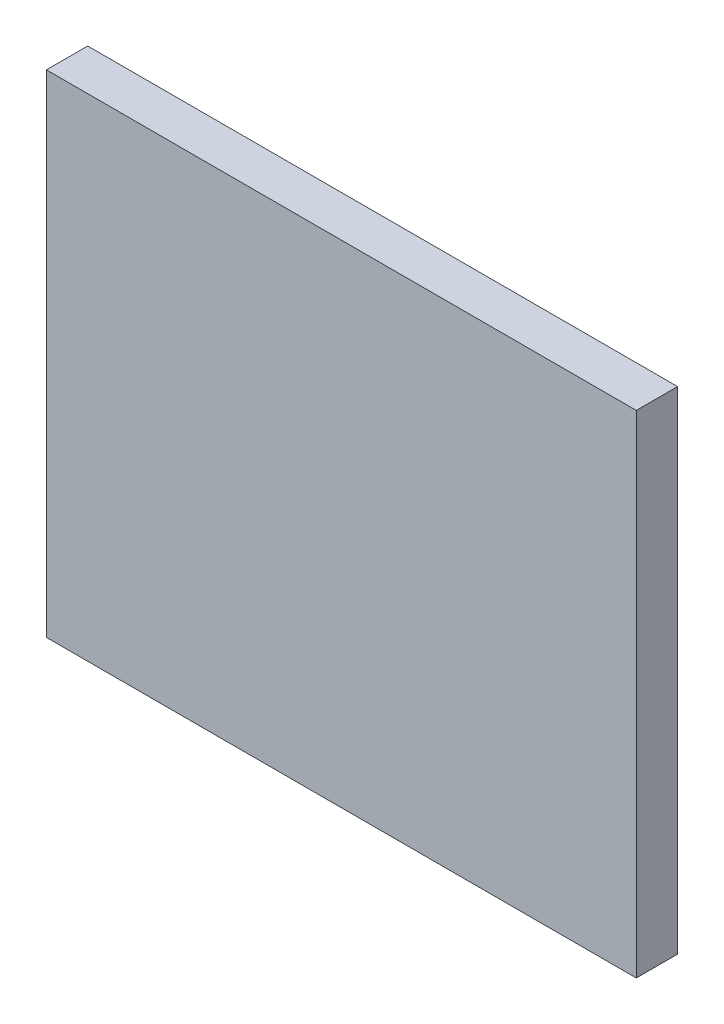
SolidWorks part; units mm, degrees
material "Buche"
ref_plane "Ebene vorne" through (0, 0, 0) normal (0, 0, 1) x (1, 0, 0)
ref_plane "Ebene oben" through (0, 0, 0) normal (0, 1, 0) x (1, 0, 0)
ref_plane "Ebene rechts" through (0, 0, 0) normal (1, 0, 0) x (0, 0, -1)
sketch "Skizze1" plane through (0, 0, 0) normal (0, 0, 1) x (1, 0, 0)
  line L1 (0, 0) -> (300, 0)
  line L2 (0, 0) -> (0, 250)
  line L3 (0, 250) -> (300, 250)
  line L4 (300, 0) -> (300, 250)
extrude "Aufsatz-Linear austragen1" add sketch "Skizze1" along normal blind 21
